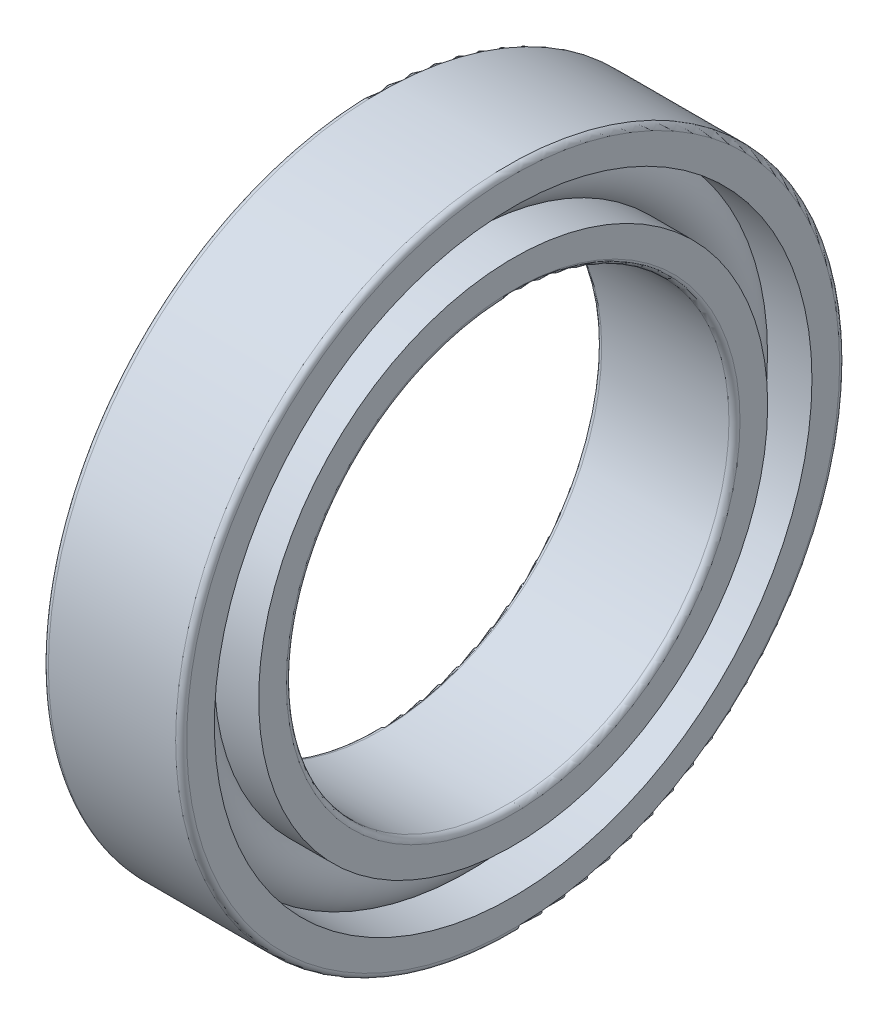
SolidWorks part; units mm, degrees
ref_plane "Plane1" through (0, 0, 0) normal (0, 0, 1) x (1, 0, 0)
ref_plane "Plane2" through (0, 0, 0) normal (0, 1, 0) x (1, 0, 0)
ref_plane "Plane3" through (0, 0, 0) normal (1, 0, 0) x (0, 0, -1)
sketch "Clipboard" plane through (0, 0, 0) normal (0, 0, 1) x (1, 0, 0)
  line L0 (-10, 0) -> (10, 0) construction
  line L1 (0, 0) -> (22.3471, -0.7804)
  line L2 (0, 0) -> (4.997, 0.1745)
  line L3 (0, 0) -> (22.3471, -0.7804)
  line L4 (0, 0) -> (-22.3573, -0.3902)
  dimension "BallCLRad" = 5
sketch "CagSpiSke" plane through (0, 0, 0) normal (0, 0, 1) x (1, 0, 0)
  line L0 (0.06, 4.9) -> (0.06, 5.1)
  line L1 (0.06, 5.1) -> (-0.06, 5.1)
  line L2 (-0.06, 5.1) -> (-0.06, 4.9)
  line L3 (-0.06, 4.9) -> (0.06, 4.9)
  line L4 (-20.6375, 0) -> (20.6375, 0) construction
  line L5 (0, 0) -> (0, 23.7692) construction
  dimension "OD" = 10.2
  dimension "ID" = 9.8
revolve "CageSpine" add sketch "CagSpiSke" angle 0.001 about L4 reverse direction yes
ref_axis "Axis1" through (-50, 0, 0) along (1, 0, 0)
sketch "CagBalSke" plane through (0, 0, 0) normal (0, 0, 1) x (1, 0, 0)
  line L0 (-0.66, 5) -> (0.66, 5)
  line L1 (-1.905, 5) -> (1.905, 5) construction
  line L2 (-10, 0) -> (10, 0) construction
  line L3 (0, 0) -> (0, 24) construction
  arc A0 (0.66, 5) -> (-0.66, 5) centre (0, 5) cw
  dimension "BallCLRad" = 5
revolve "CageBall" [suppressed] add sketch "CagBalSke" angle 360 about L1 reverse direction yes
pattern_circular "CageBalls" [suppressed] count 2 every 180 about axis through (-50, 0, 0) along (1, 0, 0)
sketch "CagTrmODSke" plane through (0, 0, 0) normal (0, 0, 1) x (1, 0, 0)
  line L0 (0.661, 5.1) -> (0.661, 5.661)
  line L1 (0.661, 5.661) -> (-0.661, 5.661)
  line L2 (-0.661, 5.661) -> (-0.661, 5.1)
  line L3 (-0.661, 5.1) -> (0.661, 5.1)
  line L4 (-20.6375, 0) -> (20.6375, 0) construction
  line L5 (0, 0) -> (0, 25) construction
  dimension "Width" = 1.322
  dimension "ID" = 10.2
  dimension "OD" = 11.322
revolve "CageTrimOD" [suppressed] cut sketch "CagTrmODSke" angle 360 about L4 reverse direction yes
sketch "CagTrmIDSke" plane through (0, 0, 0) normal (0, 0, 1) x (1, 0, 0)
  line L0 (0.661, 4.341) -> (0.661, 4.9)
  line L1 (0.661, 4.9) -> (-0.661, 4.9)
  line L2 (-0.661, 4.9) -> (-0.661, 4.341)
  line L3 (-0.661, 4.341) -> (0.661, 4.341)
  line L4 (-20.6375, 0) -> (20.6375, 0) construction
  line L5 (0, 0) -> (0, 25) construction
  dimension "Width" = 1.322
  dimension "ID" = 8.682
  dimension "OD" = 9.8
revolve "CageTrimID" [suppressed] cut sketch "CagTrmIDSke" angle 360 about L4 reverse direction yes
sketch "BalSimSke" plane through (0, 0, 0) normal (0, 0, 1) x (1, 0, 0)
  line L0 (-10, 0) -> (10, 0) construction
  line L1 (-10, 5) -> (10, 5) construction
  line L2 (0, 0) -> (0, 23) construction
  circle A0 centre (0, 5) radius 0.6
  dimension "BallCLRad" = 5
  dimension "Ball_diameter" = 1.2
revolve "BallsSimplified" add sketch "BalSimSke" angle 360 about L0
sketch "BalDetSke" plane through (0, 0, 0) normal (0, 0, 1) x (1, 0, 0)
  line L0 (-0.6, 5) -> (0.6, 5)
  line L1 (-1.905, 5) -> (1.905, 5) construction
  line L2 (0, 0) -> (0, 25) construction
  arc A0 (0.6, 5) -> (-0.6, 5) centre (0, 5) cw
  dimension "BallCLRad" = 5
  dimension "Ball_diameter" = 1.2
revolve "BallDetailed" [suppressed] add sketch "BalDetSke" angle 360 about L1 reverse direction yes
sketch "InnRacSke" plane through (0, 0, 0) normal (0, 0, 1) x (1, 0, 0)
  line L0 (-0.4131, 4.6) -> (-1.25, 4.6)
  line L1 (-1.25, 4.6) -> (-1.25, 4.1)
  line L2 (-1.15, 4) -> (1.15, 4)
  line L3 (1.25, 4.1) -> (1.25, 4.6)
  line L4 (1.25, 4.6) -> (0.4131, 4.6)
  line L5 (-20.6375, 0) -> (20.6375, 0) construction
  line L6 (0, 0) -> (0, 30) construction
  arc A0 (-1.25, 4.1) -> (-1.15, 4) centre (-1.15, 4.1) ccw
  arc A1 (1.15, 4) -> (1.25, 4.1) centre (1.15, 4.1) ccw
  arc A2 (0.4131, 4.6) -> (-0.4131, 4.6) centre (0, 5) cw
  dimension "BallCLRad" = 5
  dimension "Fillet_radius" = 0.1
  dimension "Ball_diameter" = 1.15
  dimension "ID" = 8
  dimension "OD" = 9.2
  dimension "Width" = 2.5
revolve "InnerRace" add sketch "InnRacSke" angle 360 about L5 reverse direction yes
sketch "OutRacSke" plane through (0, 0, 0) normal (0, 0, 1) x (1, 0, 0)
  line L0 (-0.4131, 5.4) -> (-1.25, 5.4)
  line L1 (-1.25, 5.4) -> (-1.25, 5.9)
  line L2 (-1.15, 6) -> (1.15, 6)
  line L3 (1.25, 5.9) -> (1.25, 5.4)
  line L4 (1.25, 5.4) -> (0.4131, 5.4)
  line L5 (-20.6375, 0) -> (20.6375, 0) construction
  line L6 (0, 0) -> (0, 30) construction
  arc A0 (-1.25, 5.9) -> (-1.15, 6) centre (-1.15, 5.9) cw
  arc A1 (1.15, 6) -> (1.25, 5.9) centre (1.15, 5.9) cw
  arc A2 (0.4131, 5.4) -> (-0.4131, 5.4) centre (0, 5) ccw
  dimension "BallCLRad" = 5
  dimension "Fillet_radius" = 0.1
  dimension "Ball_diameter" = 1.15
  dimension "Width" = 2.5
revolve "OuterRace" add sketch "OutRacSke" angle 360 about L5 reverse direction yes
pattern_circular "BallsDetailed" [suppressed] count 2 every 180 about axis through (-50, 0, 0) along (1, 0, 0)
equation "\"BallCLRad@Clipboard\" = ( \"OD@OutRacSke\" + \"ID@InnRacSke\" ) / 4"
equation "\"BallCLRad@BalSimSke\" = \"BallCLRad@Clipboard\""
equation "\"BallCLRad@BalDetSke\" = \"BallCLRad@Clipboard\""
equation "\"BallCLRad@InnRacSke\" = \"BallCLRad@Clipboard\""
equation "\"BallCLRad@OutRacSke\" = \"BallCLRad@Clipboard\""
equation "\"Ball_diameter@InnRacSke\" = \"Ball_diameter@BalDetSke\" - 0.05"
equation "\"Ball_diameter@OutRacSke\" = \"Ball_diameter@BalDetSke\" - 0.05"
equation "\"Ball_diameter@BalSimSke\" = \"Ball_diameter@BalDetSke\""
equation "\"Width@OutRacSke\" = \"Width@InnRacSke\""
equation "\"Fillet_radius@OutRacSke\" = \"Fillet_radius@InnRacSke\""
equation "\"Max_count@Clipboard\" = int( 3.14159265 / atn(( \"Ball_diameter@BalDetSke\" / 2) / sqr( \"BallCLRad@Clipboard\"  *  \"BallCLRad@Clipboard\" - ( \"Ball_diameter@BalDetSke\" / 2) *  ( \"Ball_diameter@BalDetSke\" / 2))))"
equation "\"Max_count@Clipboard\" = ((sgn( \"Max_count@Clipboard\" - \"Count@Clipboard\" )-1)*( \"Max_count@Clipboard\" - \"Count@Clipboard\" ))/-2+ \"Count@Clipboard\""
equation "\"Count@BallsDetailed\" = int( \"Show_count@Clipboard\" ) "
equation "\"Count@BallsDetailed\" = ((sgn( \"Count@BallsDetailed\" - \"Max_count@Clipboard\" )-1)*( \"Count@BallsDetailed\" - \"Max_count@Clipboard\" ))/-2+ \"Max_count@Clipboard\""
equation "\"Count@BallsDetailed\" = ((sgn( \"Count@BallsDetailed\" - \"Min_count@Clipboard\" )+1)*( \"Count@BallsDetailed\" - \"Min_count@Clipboard\"))/2 +\"Min_count@Clipboard\""
equation "\"Angle@BallsDetailed\" = 360.0 / \"Max_count@Clipboard\""
equation "\"BallCLRad@CagBalSke\" = \"BallCLRad@Clipboard\""
equation "\"Count@CageBalls\" = \"Count@BallsDetailed\""
equation "\"Angle@CageBalls\" = \"Angle@BallsDetailed\""
equation "\"Angle@CageSpine\" =  \"Angle@CageBalls\" * ( \"Count@CageBalls\" -1 + int( \"Count@CageBalls\" / \"Max_count@Clipboard\" ) )  + 0.001 -  int( \"Count@CageBalls\" / \"Max_count@Clipboard\" ) * 0.001"
equation "\"Angle@CageSpine\" =  \"Angle@CageSpine\" * int( \"Min_count@Clipboard\" / 2) + int(1 / \"Min_count@Clipboard\")  * 0.001"
equation "\"CageWallOD@CagBalSke\" =  \"Ball_diameter@BalDetSke\" * 1.1"
equation "\"Thickness@CagSpiSke\" =  \"Ball_diameter@BalDetSke\" * 0.1"
equation "\"OD@CagTrmODSke\" = \"BallCLRad@Clipboard\" * 2 + \"CageWallOD@CagBalSke\" + 0.002"
equation "\"ID@CagTrmODSke\" = \"BallCLRad@Clipboard\" * 2 + \"Ball_diameter@BalDetSke\" / 6"
equation "\"OD@CagTrmIDSke\" = \"BallCLRad@Clipboard\" * 2 - \"Ball_diameter@BalDetSke\" / 6"
equation "\"ID@CagTrmIDSke\" = \"BallCLRad@Clipboard\" * 2 - \"CageWallOD@CagBalSke\" + 0.002"
equation "\"OD@CagSpiSke\" = \"ID@CagTrmODSke\""
equation "\"ID@CagSpiSke\" = \"OD@CagTrmIDSke\""
equation "\"Width@CagTrmODSke\" = \"CageWallOD@CagBalSke\" + 0.002"
equation "\"Width@CagTrmIDSke\" = \"CageWallOD@CagBalSke\" + 0.002"
